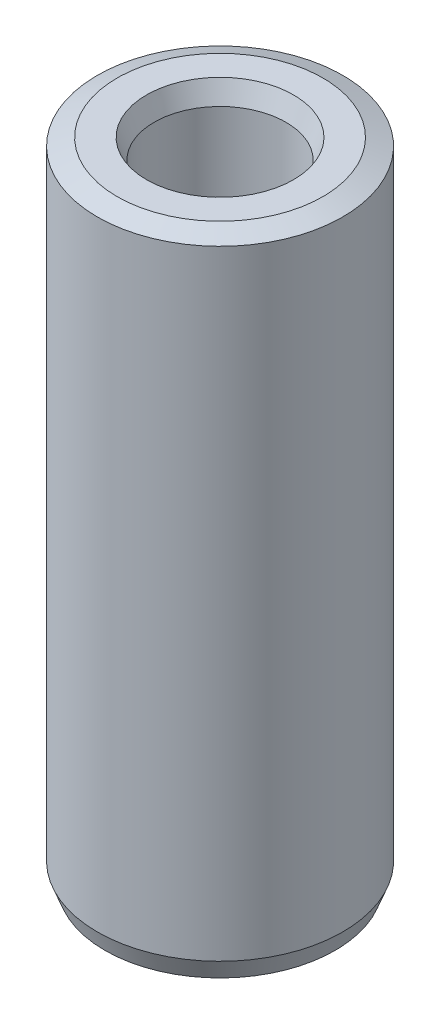
SolidWorks part; units mm, degrees
ref_plane "Front Plane" through (0, 0, 0) normal (0, 0, 1) x (1, 0, 0)
ref_plane "Top Plane" through (0, 0, 0) normal (0, 1, 0) x (1, 0, 0)
ref_plane "Right Plane" through (0, 0, 0) normal (1, 0, 0) x (0, 0, -1)
sketch "Sketch1" plane through (0, 0, 0) normal (0, 1, 0) x (1, 0, 0)
  circle A0 centre (0, 0) radius 50
  dimension "SLEEVE_OD" = 100
extrude "Boss-Extrude1" add sketch "Sketch1" along normal blind 263.5212
sketch "Sketch2" plane through (0, 0, 0) normal (0, 1, 0) x (1, 0, 0)
  circle A0 centre (0, 0) radius 26.8388
  dimension "BORE_D" = 53.6776
extrude "Cut-Extrude1" cut sketch "Sketch2" along normal through all
chamfer "Chamfer1" distance 3.1141 angle 68.945 4 edges at (0, 263.5212, 26.8388) (0, 0, 26.8388) (0, 0, 50) (0, 263.5212, 50) first distance on face at (0, 263.5212, 26.8388) first distance on face at (0, 0, 26.8388) first distance on face at (0, 263.5212, 50)
